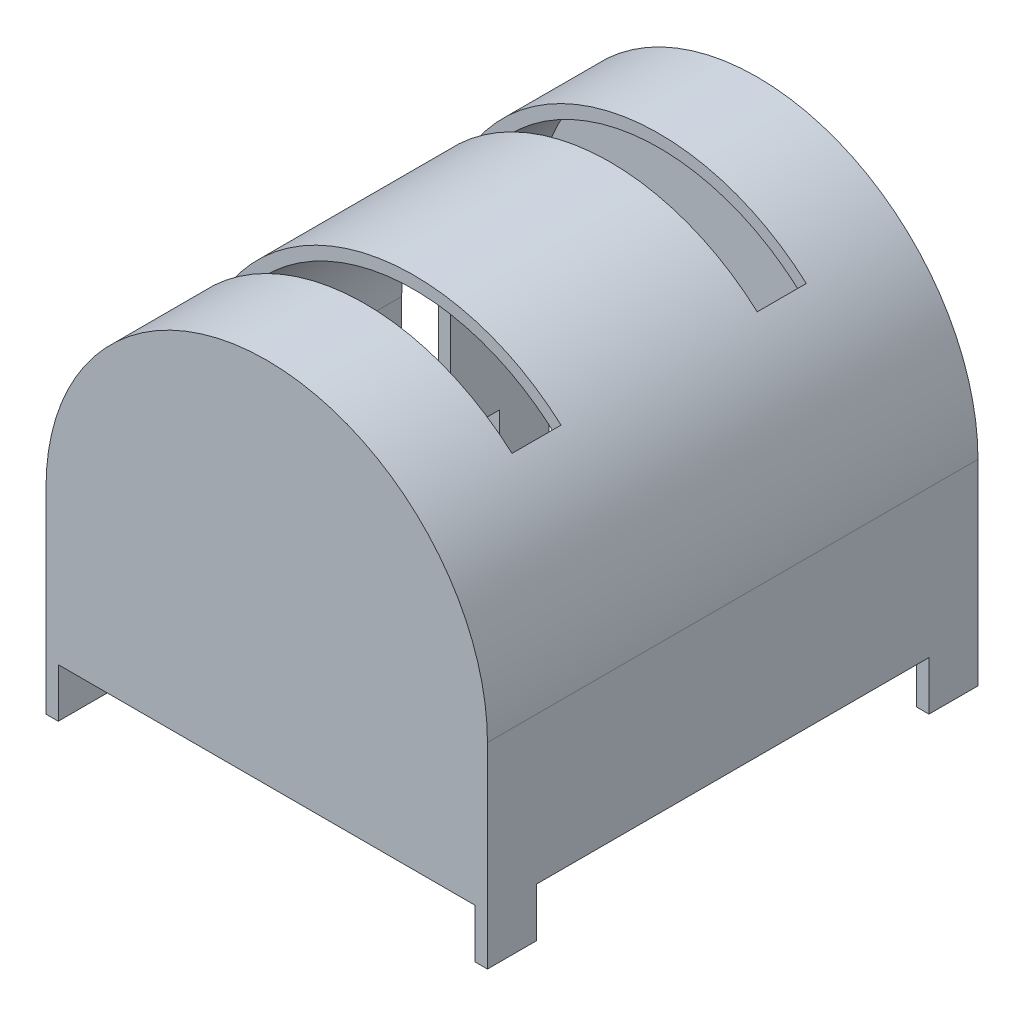
SolidWorks part; units mm, degrees
ref_plane "Front Plane" through (0, 0, 0) normal (0, 0, 1) x (1, 0, 0)
ref_plane "Top Plane" through (0, 0, 0) normal (0, 1, 0) x (1, 0, 0)
ref_plane "Right Plane" through (0, 0, 0) normal (1, 0, 0) x (0, 0, -1)
sketch "Sketch1" plane through (0, 0, 0) normal (0, 1, 0) x (1, 0, 0)
  line L1 (-42.5, 47.5) -> (42.5, 47.5)
  line L2 (-42.5, 47.5) -> (-42.5, -47.5)
  line L3 (-42.5, -47.5) -> (42.5, -47.5)
  line L4 (42.5, 47.5) -> (42.5, -47.5)
  line L5 (-45, 50) -> (45, 50)
  line L6 (-45, 50) -> (-45, -50)
  line L7 (-45, -50) -> (45, -50)
  line L8 (45, 50) -> (45, -50)
  dimension "D1" = 85
  dimension "D2" = 90
  dimension "D3" = 100
  dimension "D4" = 95
  dimension "D5" = 42.5
  dimension "D6" = 45
  dimension "D7" = 47.5
  dimension "D8" = 50
extrude "Boss-Extrude1" add sketch "Sketch1" along normal blind 30
sketch "Sketch2" plane through (0, 0, 0) normal (0, -1, 0) x (1, 0, 0)
  line L0 (-42.5, 47.5) -> (-42.5, 50)
  line L1 (-45, 50) -> (45, 50) construction
  line L2 (-42.5, 50) -> (-45, 50)
  line L3 (-45, 50) -> (-45, 40)
  line L4 (-45, -50) -> (-45, 50) construction
  line L5 (-45, 40) -> (-42.5, 40)
  line L6 (-42.5, -47.5) -> (-42.5, 47.5) construction
  line L7 (-42.5, 40) -> (-42.5, 47.5)
  line L8 (42.5, 47.5) -> (42.5, 50)
  line L9 (42.5, 50) -> (45, 50)
  line L10 (45, 50) -> (45, 40)
  line L11 (45, 50) -> (45, -50) construction
  line L12 (45, 40) -> (42.5, 40)
  line L13 (42.5, 47.5) -> (42.5, -47.5) construction
  line L14 (42.5, 40) -> (42.5, 47.5)
  line L15 (-42.5, -47.5) -> (-42.5, -40)
  line L16 (-42.5, -40) -> (-45, -40)
  line L17 (-45, -40) -> (-45, -50)
  line L18 (-45, -50) -> (-42.5, -50)
  line L19 (45, -50) -> (-45, -50) construction
  line L20 (-42.5, -50) -> (-42.5, -47.5)
  line L21 (45, -50) -> (45, -40)
  line L22 (45, -40) -> (42.5, -40)
  line L23 (42.5, -40) -> (42.5, -50)
  line L24 (42.5, -50) -> (45, -50)
  dimension "D1" = 10
  dimension "D2" = 10
  dimension "D3" = 10
  dimension "D4" = 2.5
  dimension "D5" = 10
  dimension "D6" = 10
  dimension "D7" = 10
  dimension "D8" = 10
  dimension "D9" = 10
  dimension "D10" = 2.5
  dimension "D11" = 2.5
extrude "Boss-Extrude2" add sketch "Sketch2" along normal blind 10
sketch "Sketch3" plane through (0, 30, 0) normal (0, 1, 0) x (1, 0, 0)
  line L0 (0, 57.6639) -> (0, -57.6639)
  point P4 (0, 0)
ref_axis "Axis1" through (0, 30, -57.6639) along (0, 0, 1)
sketch "Sketch4" plane through (0, 30, 0) normal (0, 1, 0) x (1, 0, 0)
  line L0 (45, 50) -> (45, -50)
  line L1 (45, -50) -> (0, -50)
  line L2 (-45, -50) -> (45, -50) construction
  line L3 (0, -50) -> (0, -47.5)
  line L4 (-42.5, -47.5) -> (42.5, -47.5) construction
  line L5 (0, -47.5) -> (42.5, -47.5)
  line L6 (42.5, -47.5) -> (42.5, 47.5)
  line L7 (42.5, 47.5) -> (0, 47.5)
  line L8 (42.5, 47.5) -> (-42.5, 47.5) construction
  line L9 (0, 47.5) -> (0, 50)
  line L10 (45, 50) -> (-45, 50) construction
  line L11 (0, 50) -> (45, 50)
revolve "Revolve1" add sketch "Sketch4" angle 180 about L0
sketch "Sketch5" plane through (0, 0, 0) normal (0, 1, 0) x (1, 0, 0)
  line L1 (-90, 30) -> (30, 30)
  line L2 (-90, 30) -> (-90, -30)
  line L3 (-90, -30) -> (30, -30)
  line L4 (30, 30) -> (30, -30)
  line L5 (-80, 20) -> (30, 20)
  line L6 (-80, 20) -> (-80, -20)
  line L7 (-80, -20) -> (30, -20)
  line L8 (30, 20) -> (30, -20)
  line L10 (30, 10) -> (-80, 10)
  line L11 (-80, 10) -> (-80, -10)
  line L12 (-80, -10) -> (30, -10)
  line L13 (30, -10) -> (30, 10)
  dimension "D1" = 40
  dimension "D2" = 20
  dimension "D3" = 60
  dimension "D4" = 30
  dimension "D5" = 120
  dimension "D6" = 110
  dimension "D7" = 30
  dimension "D8" = 30
  dimension "D9" = 20
  dimension "D10" = 10
extrude "Cut-Extrude1" cut sketch "Sketch5" along normal through all contours L7 L6 L5 L4 L1 L2 L3 region at (-30, 0, -28.6584)
